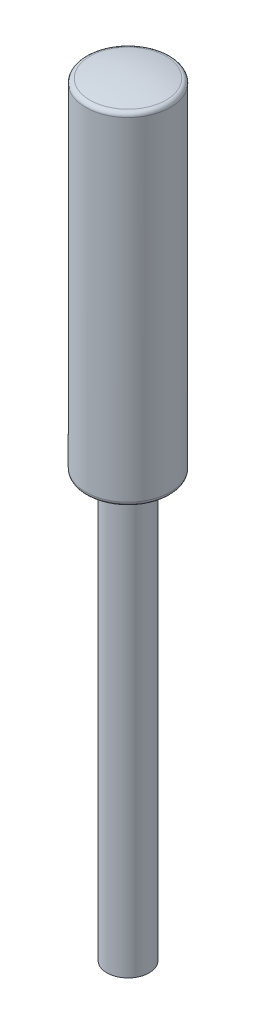
SolidWorks part; units mm, degrees
ref_plane "Front Plane" through (0, 0, 0) normal (0, 0, 1) x (1, 0, 0)
ref_plane "Top Plane" through (0, 0, 0) normal (0, 1, 0) x (1, 0, 0)
ref_plane "Right Plane" through (0, 0, 0) normal (1, 0, 0) x (0, 0, -1)
sketch "Sketch1" plane through (0, 0, 0) normal (0, 0, 1) x (1, 0, 0)
  line L0 (0, 0) -> (5, 0)
  line L1 (5, 0) -> (5, -40.4)
  line L2 (5, -40.4) -> (2.5, -40.4)
  line L3 (2.5, -40.4) -> (2.5, -90.4)
  line L4 (2.5, -90.4) -> (0, -90.4)
  line L5 (0, -90.4) -> (0, 0)
  dimension "D1" = 5
  dimension "D2" = 40.4
  dimension "D3" = 2.5
  dimension "D4" = 50
revolve "Revolve1" add sketch "Sketch1" angle 360 about L5
fillet "Fillet1" radius 0.5 2 edges at (0, -40.4, -5) (0, 0, -5)
dome "Dome1" faces to dome 1 distance 0.5 reverse direction no elliptical dome no face at (0, 0, 4.5) parameters "D1"=0.5
